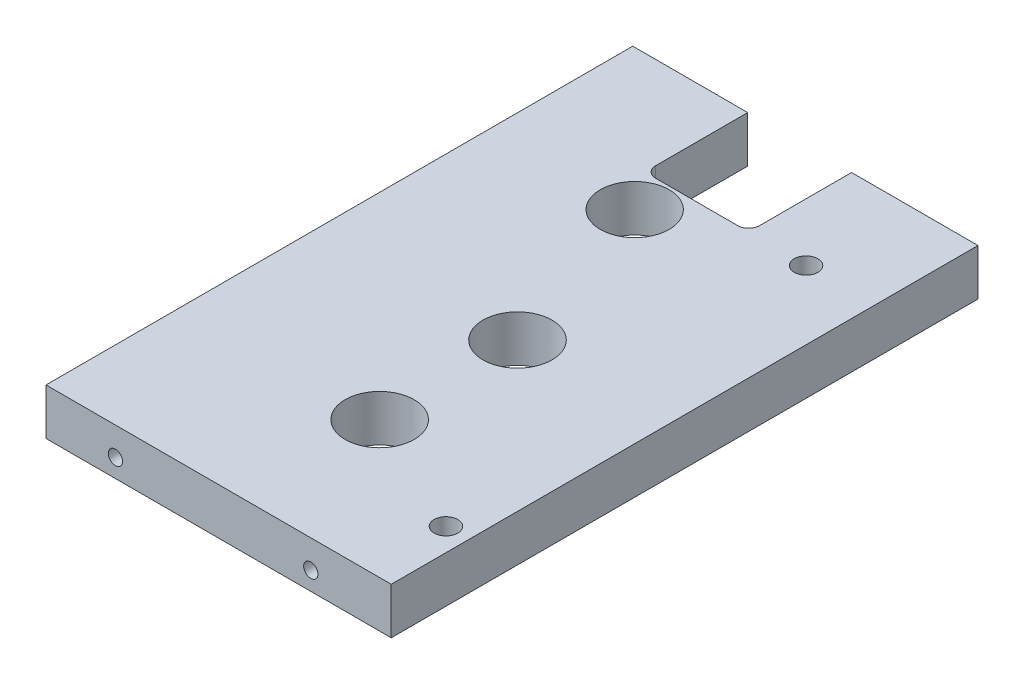
SolidWorks part; units mm, degrees
material "1060 Alloy"
ref_plane "Front Plane" through (0, 0, 0) normal (0, 0, 1) x (1, 0, 0)
ref_plane "Top Plane" through (0, 0, 0) normal (0, 1, 0) x (1, 0, 0)
ref_plane "Right Plane" through (0, 0, 0) normal (1, 0, 0) x (0, 0, -1)
sketch "Sketch1" plane through (0, 0, 0) normal (0, 0, 1) x (1, 0, 0)
  line L0 (-234.625, -82.5) -> (-329.875, -82.5) construction
  line L1 (-234.625, -88.9) -> (-329.875, -88.9)
  line L2 (-234.625, -88.9) -> (-234.625, -76.1)
  line L3 (-234.625, -76.1) -> (-329.875, -76.1)
  line L4 (-329.875, -88.9) -> (-329.875, -76.1)
  line L7 (-329.875, -610.1) -> (-329.875, -622.9) construction
  line L8 (-234.625, -610.1) -> (-234.625, -622.9) construction
  circle A0 centre (-308, -82.5) radius 3.1
  circle A1 centre (-320.5, -82.5) radius 2.395
  circle A2 centre (-244.2, -82.5) radius 2.395
  circle A3 centre (-257.2, -82.5) radius 3.1
  circle A9 centre (-308, -82.5) radius 3.1 construction
  circle A10 centre (-257.2, -82.5) radius 3.1 construction
  circle A11 centre (-244.2, -82.5) radius 3.425 construction
  circle A12 centre (-320.5, -82.5) radius 3.425 construction
  circle A13 centre (-320.5, -616.5) radius 2.395 construction
extrude "Boss-Extrude1" add sketch "Sketch1" along normal up to surface (161.88 mm away) contours L3 L4 L1 L2
extrude "Cut-Extrude1" cut sketch "Sketch1<3>" along normal up to surface (20.2 mm away) contours A0 L0 | A3 L0 | L0 A0 | L0 A3 region at (-257.2, -83.8157, 0) region at (-257.2, -81.1843, 0) region at (-308, -83.8157, 0) region at (-308, -81.1843, 0)
sketch "Sketch1<3>" plane through (0, 0, 0) normal (0, 0, 1) x (1, 0, 0) same geometry as "Sketch1"
extrude "Cut-Extrude2" cut sketch "Sketch1<4>" along normal up to surface (21.5 mm away) contours L0 A2 | A2 L0 | L0 A1 | A1 L0 region at (-244.2, -83.5165, 0) region at (-244.2, -81.4835, 0) region at (-320.5, -81.4835, 0) region at (-320.5, -83.5165, 0)
sketch "Sketch1<4>" plane through (0, 0, 0) normal (0, 0, 1) x (1, 0, 0) same geometry as "Sketch1"
sketch "Sketch2" plane through (0, -76.1, 0) normal (0, 1, 0) x (-1, 0, 0)
  line L3 (269.505, 25.4) -> (269.505, 0)
  line L4 (295.155, 28.4) -> (272.505, 28.4)
  line L5 (298.155, 0) -> (298.155, 25.4)
  line L6 (269.505, 0) -> (298.155, 0)
  line L7 (295.155, 28.4) -> (272.505, 28.4) construction
  line L8 (269.505, 25.4) -> (269.505, 0) construction
  line L9 (298.155, 0) -> (298.155, 25.4) construction
  line L10 (234.625, 0) -> (329.875, 0) construction
  arc A6 (272.505, 28.4) -> (269.505, 25.4) centre (272.505, 25.4) ccw
  arc A7 (298.155, 25.4) -> (295.155, 28.4) centre (295.155, 25.4) ccw
  circle A8 centre (275.57, 86.105) radius 9.525
  circle A9 centre (275.57, 124.135) radius 9.525
  circle A10 centre (253.55, 28.505) radius 3.265
  circle A11 centre (240.925, 140.49) radius 3.265
  arc A12 (272.505, 28.4) -> (269.505, 25.4) centre (272.505, 25.4) ccw construction
  arc A13 (298.155, 25.4) -> (295.155, 28.4) centre (295.155, 25.4) ccw construction
  circle A14 centre (275.57, 86.105) radius 9.525 construction
  circle A15 centre (275.57, 124.135) radius 9.525 construction
  circle A16 centre (240.925, 140.49) radius 3.265 construction
  circle A17 centre (253.55, 28.505) radius 3.265 construction
extrude "Cut-Extrude3" cut sketch "Sketch2" against normal up to next
sketch "Sketch3" plane through (0, -88.9, 0) normal (0, -1, 0) x (1, 0, 0)
  circle A2 centre (-240.925, 140.49) radius 3.265
  circle A3 centre (-253.55, 28.505) radius 9.525
  circle A4 centre (-253.55, 28.505) radius 9.525 construction
  circle A6 centre (-240.925, 140.49) radius 3.265 construction
extrude "Cut-Extrude4" cut sketch "Sketch3" against normal blind 3.32
sketch "Sketch4" plane through (0, 0, 161.88) normal (0, 0, 1) x (1, 0, 0)
  circle A0 centre (-256.825, -83.83) radius 1.965
  circle A1 centre (-310.715, -83.83) radius 1.965
  circle A5 centre (-256.825, -83.83) radius 2.795 construction
  circle A6 centre (-310.715, -83.83) radius 2.795 construction
  dimension "D1" = 3.93
extrude "Cut-Extrude5" cut sketch "Sketch4" against normal up to surface (17.25 mm away)
ref_plane "Plane1" through (0, -82.5, 0) normal (0, 1, 0) x (-1, 0, 0)
sketch "Sketch5" plane through (0, -82.5, 0) normal (0, 1, 0) x (-1, 0, 0)
  line L9 (234.625, 57.29) -> (259.3185, 57.29) construction
  line L10 (234.625, 57.29) -> (221.025, 57.29) construction
  line L11 (221.025, 57.29) -> (221.025, 54.59) construction
  line L12 (232.2758, 52.475) -> (228.8458, 52.475) construction
  line L13 (232.295, 52.925) -> (232.2758, 52.475) construction
  line L14 (233.835, 52.925) -> (232.295, 52.925) construction
  line L15 (233.835, 52.09) -> (233.835, 52.925) construction
  line L16 (234.625, 52.09) -> (233.835, 52.09) construction
  line L17 (234.625, 57.29) -> (234.625, 52.09) construction
  line L18 (234.625, 57.29) -> (259.3185, 57.29) construction
  line L19 (234.625, 57.29) -> (221.025, 57.29)
  line L20 (221.025, 57.29) -> (221.025, 54.59)
  line L21 (232.2758, 52.475) -> (228.8458, 52.475)
  line L22 (232.295, 52.925) -> (232.2758, 52.475)
  line L23 (233.835, 52.925) -> (232.295, 52.925)
  line L24 (233.835, 52.09) -> (233.835, 52.925)
  line L25 (234.625, 52.09) -> (233.835, 52.09)
  line L26 (234.625, 57.29) -> (234.625, 52.09)
  arc A1 (221.025, 54.59) -> (228.8458, 52.475) centre (230.8458, 75.3879) ccw construction
  arc A2 (221.025, 54.59) -> (228.8458, 52.475) centre (230.8458, 75.3879) ccw
sketch "Sketch6" plane through (0, -76.1, 0) normal (0, 1, 0) x (-1, 0, 0)
  circle A0 centre (290.57, 38.77) radius 9.5
  circle A1 centre (290.57, 38.77) radius 3 construction
  dimension "D1" = 19
extrude "Cut-Extrude6" cut sketch "Sketch6" against normal through all
